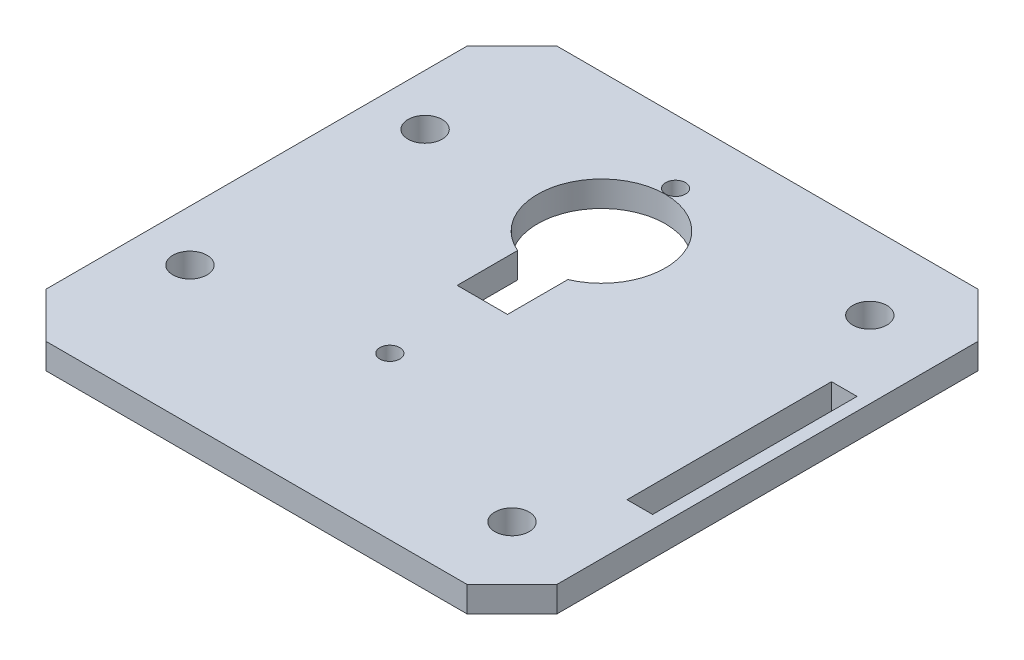
SolidWorks part; units mm, degrees
note: The reader was unsure of these and kept them because the rebuilt part matched: shared geometry of "Sketch17<6>".
material "ABS"
ref_plane "Front Plane" through (0, 0, 0) normal (0, 0, 1) x (1, 0, 0)
ref_plane "Top Plane" through (0, 0, 0) normal (0, 1, 0) x (1, 0, 0)
ref_plane "Right Plane" through (0, 0, 0) normal (1, 0, 0) x (0, 0, -1)
sketch "Sketch1" plane through (0, 0, 0) normal (0, 1, 0) x (1, 0, 0)
  line L1 (-25.4, -25.4) -> (25.4, -25.4)
  line L2 (-25.4, -25.4) -> (-25.4, 25.4)
  line L3 (-25.4, 25.4) -> (25.4, 25.4)
  line L4 (25.4, -25.4) -> (25.4, 25.4)
  line L5 (-25.4, -25.4) -> (25.4, 25.4) construction
  line L6 (-25.4, 25.4) -> (25.4, -25.4) construction
  point P0 (0, 0)
  dimension "D1" = 50.8
extrude "Boss-Extrude1" add sketch "Sketch1" along normal blind 2.54
sketch "Sketch3" plane through (0, 2.54, 0) normal (0, 1, 0) x (1, 0, 0)
  line L0 (-25.4, 0) -> (25.4, 0) construction
  line L1 (-25.4, 25.4) -> (-25.4, -25.4) construction
  line L2 (25.4, -25.4) -> (25.4, 25.4) construction
  line L3 (0, -25.4) -> (0, 25.4) construction
  line L4 (-25.4, -25.4) -> (25.4, -25.4) construction
  line L5 (25.4, 25.4) -> (-25.4, 25.4) construction
  point P12 (-20.32, -11.684)
  point P13 (-20.32, 11.684)
  dimension "D1" = 5.08
  dimension "D2" = 11.684
  dimension "D3" = 11.684
  dimension "D4" = 5.08
hole_wizard "holes for arms" positions "Sketch7" profile "Sketch8" hole size "M3" standard "ANSI Metric" end condition through all
sketch "Sketch7" plane through (0, 2.54, 0) normal (0, 1, 0) x (1, 0, 0)
  point P0 (-20.32, -11.684)
  point P3 (-20.32, 11.684)
sketch "Sketch8" plane through (-20.32, 2.54, 11.684) normal (1, 0, 0) x (0, 0, 1)
  line L0 (0, 0) -> (0, 2.54)
  line L1 (0, 2.54) -> (1.7, 2.54)
  line L2 (1.7, 2.54) -> (1.7, 0)
  line L5 (1.7, 0) -> (0, 0)
  line L11 (0, -6.35) -> (0, 107.95) construction
  dimension "Thru Hole Dia." = 3.4
  dimension "Thru Hole Depth" = 2.54
sketch "Sketch9" plane through (0, 2.54, 0) normal (0, 1, 0) x (1, 0, 0)
  line L0 (-25.4, -25.4) -> (25.4, -25.4) construction
  line L1 (25.4, -25.4) -> (25.4, 25.4) construction
  line L2 (25.4, 0) -> (-25.4, 0) construction
  point P0 (17.78, -17.78)
  point P9 (17.78, 17.78)
  dimension "D1" = 7.62
  dimension "D2" = 7.62
hole_wizard "holes for structure" positions "Sketch10" profile "Sketch11" hole size "M3" standard "ANSI Metric" end condition through all
sketch "Sketch10" plane through (0, 2.54, 0) normal (0, 1, 0) x (1, 0, 0)
  line L0 (-25.4, 0) -> (25.4, 0) construction
  circle A0 centre (17.78, -17.78) radius 3.81
  circle A1 centre (17.78, 17.78) radius 3.81
  point P0 (17.78, -17.78)
  point P3 (17.78, 17.78)
  dimension "D1" = 7.62
sketch "Sketch11" plane through (17.78, 2.54, 17.78) normal (1, 0, 0) x (0, 0, 1)
  line L0 (0, 0) -> (0, 2.54)
  line L1 (0, 2.54) -> (1.7, 2.54)
  line L2 (1.7, 2.54) -> (1.7, 0)
  line L5 (1.7, 0) -> (0, 0)
  line L11 (0, -6.35) -> (0, 107.95) construction
  dimension "Thru Hole Dia." = 3.4
  dimension "Thru Hole Depth" = 2.54
sketch "Sketch12" plane through (0, 2.54, 0) normal (0, 1, 0) x (1, 0, 0)
  line L0 (0, -25.4) -> (0, 25.4) construction
  line L1 (-25.4, 0) -> (25.4, 0) construction
  line L2 (-20.9099, -25.4) -> (-25.4, -20.9099)
  line L3 (-25.4, -25.4) -> (25.4, -25.4) construction
  line L4 (-25.4, 25.4) -> (-25.4, -25.4) construction
  line L5 (-25.4, -25.4) -> (-25.4, -20.9099) construction
  line L6 (-25.4, -25.4) -> (-20.9099, -25.4) construction
  line L7 (-20.9099, 25.4) -> (-25.4, 20.9099)
  line L8 (20.9099, 25.4) -> (25.4, 20.9099)
  line L9 (20.9099, -25.4) -> (25.4, -20.9099)
  dimension "D1" = 45
  dimension "D2" = 45
  dimension "D3" = 6.35
extrude "corners" cut sketch "Sketch12" against normal blind 2.54 and the other way through all contours L2
ref_plane "Plane1" through (0, 0, 0) normal (-1, 0, 0) x (0, 0, 1)
ref_plane "Plane2" through (0, 0, 0) normal (0, 0, -1) x (-1, 0, 0)
mirror "mirror of corner" about plane through (0, 0, 0) normal (-1, 0, 0) of "corners"
mirror "mirror of corner 2" about plane through (0, 0, 0) normal (0, 0, -1) of "mirror of corner", "corners"
sketch "Sketch14" plane through (0, 2.54, 0) normal (0, 1, 0) x (1, 0, 0)
  line L0 (0, -25.4) -> (0, 25.4) construction
  line L1 (-25.4, 0) -> (25.4, 0) construction
  line L2 (-6.35, -25.4) -> (6.35, -25.4)
  line L3 (-20.9099, -25.4) -> (20.9099, -25.4) construction
  line L4 (-6.35, -25.4) -> (-3.4171, -20.32)
  line L5 (-3.4171, -20.32) -> (3.4171, -20.32)
  line L6 (6.35, -25.4) -> (3.4171, -20.32)
  line L7 (-6.35, 25.4) -> (-3.4171, 20.32)
  line L8 (-6.35, 25.4) -> (6.35, 25.4)
  line L9 (6.35, 25.4) -> (3.4171, 20.32)
  line L10 (-3.4171, 20.32) -> (3.4171, 20.32)
  point P14 (0, -20.32)
  dimension "D1" = 6.35
  dimension "D2" = 5.08
  dimension "D3" = 60
sketch "Sketch15" plane through (0, 2.54, 0) normal (0, 1, 0) x (1, 0, 0)
  line L0 (-25.4, 0) -> (25.4, 0) construction
  line L1 (-21.2597, 2.54) -> (-21.2597, -2.54)
  line L2 (-21.2597, -2.54) -> (-18.2326, -5.08)
  line L3 (-18.2326, -5.08) -> (-5.5326, -5.08)
  line L4 (-5.5326, -5.08) -> (-1.27, 0)
  line L5 (-5.5326, 5.08) -> (-1.27, 0)
  line L6 (-21.2597, 2.54) -> (-18.2326, 5.08)
  line L7 (-18.2326, 5.08) -> (-5.5326, 5.08)
  line L8 (0, -25.4) -> (0, 25.4) construction
  point P12 (-21.2597, 0)
  dimension "D1" = 12.7
  dimension "D2" = 2.54
  dimension "D3" = 130
  dimension "D4" = 130
  dimension "D5" = 19.9897
  dimension "D6" = 5.08
  dimension "D7" = 1.27
sketch "Sketch16" plane through (0, 2.54, 0) normal (0, 1, 0) x (1, 0, 0)
  line L0 (24.13, -12.7) -> (21.59, -12.7)
  line L2 (21.59, -12.7) -> (21.59, 12.7)
  line L3 (-25.4, 0) -> (25.4, 0) construction
  line L4 (24.13, -12.7) -> (24.13, 12.7)
  line L5 (1.397, 0) -> (-1.397, 0) construction
  line L6 (24.13, 12.7) -> (21.59, 12.7)
  line L7 (21.59, 7.62) -> (24.13, 7.62)
  line L8 (21.59, -10.16) -> (24.13, -10.16)
  line L9 (21.59, -10.16) -> (21.59, -7.62)
  line L10 (21.59, -7.62) -> (24.13, -7.62)
  line L11 (24.13, -10.16) -> (24.13, -7.62)
  line L12 (24.13, 10.16) -> (24.13, 7.62)
  line L13 (21.59, 10.16) -> (24.13, 10.16)
  line L14 (21.59, 10.16) -> (21.59, 7.62)
  line L15 (25.4, -20.9099) -> (25.4, 20.9099) construction
  point P8 (21.59, 0)
  point P13 (25.4, 0)
  dimension "D1" = 2.54
  dimension "D2" = 12.7
  dimension "D3" = 2.54
  dimension "D4" = 2.54
  dimension "D5" = 1.27
extrude "Cut-Extrude1" cut sketch "Sketch16" against normal blind 2.54 contours L10 L2 L8 L4 | L13 L2 L7 L4
sketch "Sketch17" plane through (0, 2.54, 0) normal (0, 1, 0) x (1, 0, 0)
  line L1 (-20.32, 11.684) -> (16.1679, 11.684) construction
  line L3 (-25.4, 20.9099) -> (-25.4, -20.9099) construction
  circle A2 centre (-2.794, 11.684) radius 1.905
  point P5 (4.572, 11.684)
  point P10 (-25.3314, 0.8355)
  dimension "D1" = 17.526
  dimension "D2" = 3.81
extrude "Boss-Extrude4" add sketch "Sketch17" against normal through all contours A2
extrude "Cut-Extrude2" cut sketch "Sketch17<6>" against normal through all
sketch "Sketch17<6>" plane through (0, 2.54, 0) normal (0, 1, 0) x (1, 0, 0) same geometry as "Sketch17"
sketch "Sketch18" plane through (0, 2.54, 0) normal (0, 1, 0) x (1, 0, 0)
  line L0 (-2.794, 11.684) -> (-2.794, 23.3892) construction
  line L1 (-25.4, 20.9099) -> (-25.4, -20.9099) construction
  line L2 (-2.794, 11.684) -> (-2.794, -15.3027) construction
  line L9 (-5.294, 5.8468) -> (-5.294, -0.1532)
  line L10 (-5.294, -0.1532) -> (-0.294, -0.1532)
  line L11 (-0.294, 5.8468) -> (-0.294, -0.1532)
  circle A0 centre (-2.794, 19.05) radius 0.9906
  circle A1 centre (-2.794, -9.3472) radius 0.9906
  arc A2 (-0.294, 5.8468) -> (-5.294, 5.8468) centre (-2.794, 11.684) ccw
  point P7 (-2.794, -8.3566)
  point P11 (-2.794, 18.0594)
  dimension "D2" = 1.9812
  dimension "D3" = 1.9812
  dimension "D4" = 7.366
  dimension "D6" = 12.7
  dimension "D1" = 26.416
  dimension "D5" = 28.3972
  dimension "D7" = 5
  dimension "D8" = 6
  dimension "D9" = 5
extrude "Cut-Extrude3" cut sketch "Sketch18" against normal blind 2.54
sketch "Sketch19" plane through (0, 2.54, 0) normal (0, 1, 0) x (1, 0, 0)
  line L1 (21.59, 7.62) -> (24.13, 7.62)
  line L2 (21.59, 7.62) -> (21.59, -7.62)
  line L3 (21.59, -7.62) -> (24.13, -7.62)
  line L4 (24.13, 7.62) -> (24.13, -7.62)
extrude "Cut-Extrude4" cut sketch "Sketch19" against normal through all
equation "\"k\"= 1.00in"
